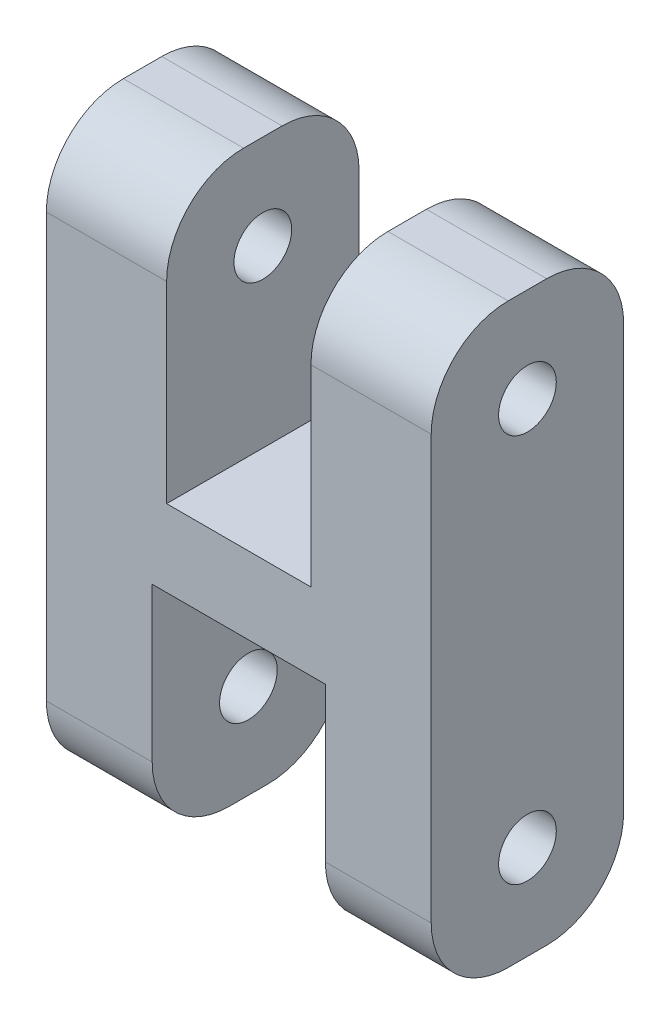
SolidWorks part; units mm, degrees
ref_plane "Alzado" through (0, 0, 0) normal (0, 0, 1) x (1, 0, 0)
ref_plane "Planta" through (0, 0, 0) normal (0, 1, 0) x (1, 0, 0)
ref_plane "Vista lateral" through (0, 0, 0) normal (1, 0, 0) x (0, 0, -1)
sketch "Croquis1" plane through (0, 0, 0) normal (1, 0, 0) x (0, 0, -1)
  line L0 (-5, 0) -> (5, 0) construction
  line L1 (-1, 15) -> (1, 15)
  line L2 (-5, 11) -> (-5, -11)
  line L3 (-1, -15) -> (1, -15)
  line L4 (5, 11) -> (5, -11)
  line L5 (-5, 15) -> (5, -15) construction
  line L6 (-5, -15) -> (5, 15) construction
  arc A0 (-5, -11) -> (-1, -15) centre (-1, -11) ccw
  arc A1 (1, -15) -> (5, -11) centre (1, -11) ccw
  arc A2 (-1, 15) -> (-5, 11) centre (-1, 11) ccw
  arc A3 (1, 15) -> (5, 11) centre (1, 11) cw
  circle A4 centre (0, 10.1) radius 1.5
  circle A5 centre (0, -10.1) radius 1.5
  point P0 (0, 0)
  dimension "D3" = 4
  dimension "D5" = 3
  dimension "D1" = 30
  dimension "D2" = 10
  dimension "D4" = 4.9
extrude "Saliente-Extruir1" add sketch "Croquis1" along normal mid plane 20
sketch "Croquis2" plane through (0, 0, 0) normal (0, 0, 1) x (1, 0, 0)
  line L5 (10, -15) -> (-10, -15) construction
  line L6 (-4.5, -15) -> (4.5, -15)
  line L7 (-4.5, -15) -> (-4.5, -3)
  line L8 (-4.5, -3) -> (4.5, -3)
  line L9 (4.5, -15) -> (4.5, -3)
  line L10 (-10, 0) -> (10, 0) construction
  line L11 (-10, 11) -> (-10, -11) construction
  line L12 (10, 11) -> (10, -11) construction
  line L13 (10, 15) -> (-10, 15) construction
  line L15 (-3.75, 15) -> (-3.75, 1)
  line L17 (3.75, 15) -> (3.75, 1)
  line L23 (-3.75, 15) -> (3.75, 15)
  line L24 (-3.75, 1) -> (3.75, 1)
  point P18 (0, -3)
  point P20 (0, 1)
  dimension "D1" = 9
  dimension "D2" = 12
  dimension "D3" = 7.5
  dimension "D4" = 14
extrude "Cortar-Extruir1" cut sketch "Croquis2" against normal through all both and the other way through all
